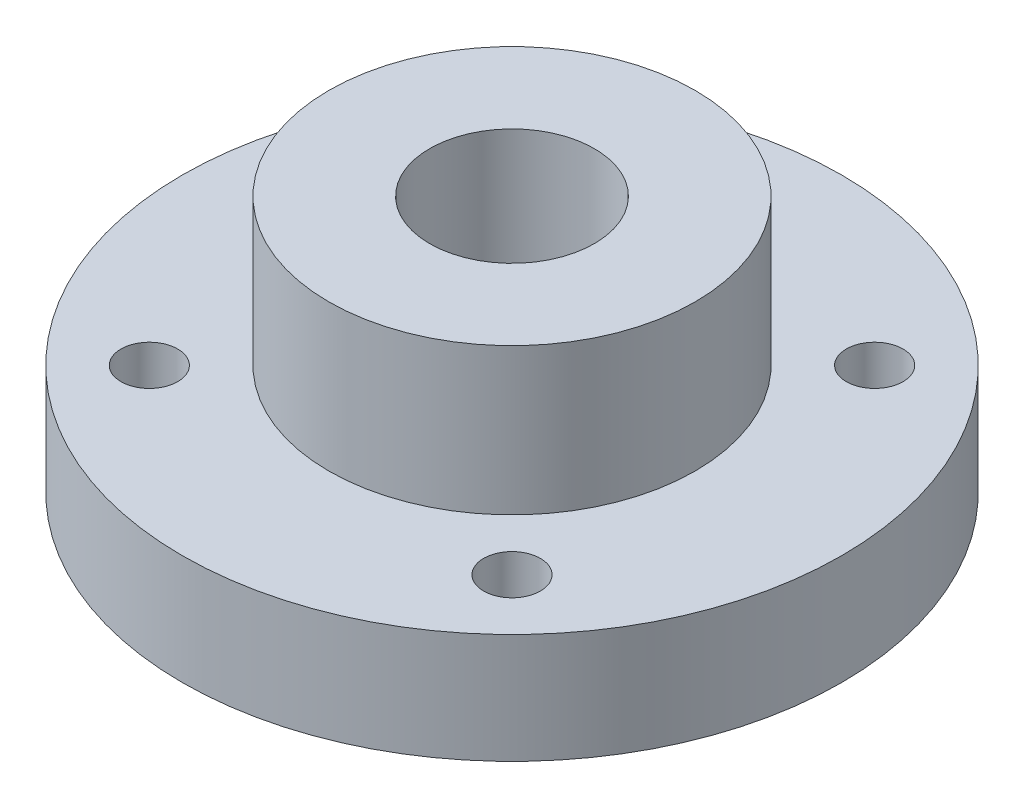
SolidWorks part; units mm, degrees
material "6061-T6 (SS)"
ref_plane "Front Plane" through (0, 0, 0) normal (0, 0, 1) x (1, 0, 0)
ref_plane "Top Plane" through (0, 0, 0) normal (0, 1, 0) x (1, 0, 0)
ref_plane "Right Plane" through (0, 0, 0) normal (1, 0, 0) x (0, 0, -1)
sketch "Sketch1" plane through (0, 0, 0) normal (0, 0, 1) x (1, 0, 0)
  line L0 (0, 0) -> (0, -14.566) construction
  line L6 (-11.1125, -70.6552) -> (-11.1125, -77.0052)
  line L7 (-15.875, -51.6052) -> (-15.875, -64.3052)
  line L8 (-15.875, -64.3052) -> (-28.575, -64.3052)
  line L9 (-28.575, -64.3052) -> (-28.575, -73.8302)
  line L12 (76.2, -73.8302) -> (-76.2, -73.8302) construction
  line L14 (-14.1605, -73.8302) -> (-14.1605, -77.0052)
  line L15 (-14.1605, -77.0052) -> (-11.1125, -77.0052)
  line L17 (-28.575, -73.8302) -> (-19.05, -73.8302)
  line L18 (-19.05, -73.8302) -> (-19.05, -70.6933)
  line L19 (-19.05, -70.6933) -> (-14.1605, -70.6933)
  line L20 (-14.1605, -70.6933) -> (-14.1605, -73.8302)
  line L21 (-15.875, -51.6052) -> (-4.7625, -51.6052)
  line L22 (-4.7625, -51.6052) -> (-4.7625, -70.6552)
  line L23 (-4.7625, -70.6552) -> (-11.1125, -70.6552)
  dimension "D2" = 22.225
  dimension "D3" = 9.525
  dimension "D4" = 9.525
  dimension "D5" = 6.35
  dimension "D6" = 12.7
  dimension "D7" = 57.15
  dimension "D8" = 19.05
  dimension "D9" = 28.321
  dimension "D11" = 3.175
  dimension "D12" = 38.1
  dimension "D13" = 3.1369
revolve "Revolve1" add sketch "Sketch1" angle 360 about L0
hole_wizard "#10 (0.1935) Diameter Hole1" positions "Sketch2" profile "Sketch3" hole size "#10" standard "ANSI Inch" end condition through all
sketch "Sketch2" plane through (0, -51.6052, 0) normal (0, 1, 0) x (1, 0, 0)
  line L0 (-15.7154, 15.7154) -> (15.7154, -15.7154) construction
  line L2 (15.7154, 15.7154) -> (-15.7154, -15.7154) construction
  line L3 (0, 0) -> (-24.6236, 0) construction
  point P0 (15.7154, 15.7154)
  point P2 (-15.7154, 15.7154)
  point P4 (-15.7154, -15.7154)
  point P6 (15.7154, -15.7154)
  dimension "D1" = 44.45
  dimension "D2" = 45
sketch "Sketch3" plane through (15.7154, -51.6052, -15.7154) normal (1, 0, 0) x (0, 0, 1)
  line L0 (0, 0) -> (0, 25.4)
  line L1 (0, 25.4) -> (2.4574, 25.4)
  line L2 (2.4574, 25.4) -> (2.4574, 0)
  line L5 (2.4574, 0) -> (0, 0)
  line L11 (0, -6.35) -> (0, 107.95) construction
  dimension "Thru Hole Dia." = 4.9149
  dimension "Thru Hole Depth" = 25.4
hole_wizard "Pipe Tap Drill for 3/8 Tap1" positions "3DSketch1" profile "Sketch4" hole size "3/8" standard "ANSI Inch"
sketch3d "3DSketch1"
  circle A1 centre (0, -51.6052, 0) radius 15.875 construction
  point P0 (0, -51.6052, 0)
  point P9 (0, -35.7302, 0)
sketch "Sketch4" plane through (0, -51.6052, 0) normal (1, 0, 0) x (0, 0, 1)
  line L0 (0, 0) -> (0, 18.5761)
  line L1 (0, 18.5761) -> (7.1374, 14.2875)
  line L2 (7.1374, 14.2875) -> (7.1374, 0)
  line L5 (7.1374, 0) -> (0, 0)
  line L10 (0, 18.5761) -> (-7.1374, 14.2875) construction
  line L11 (0, -6.35) -> (0, 107.95) construction
  dimension "Hole Dia." = 14.2748
  dimension "Hole Depth" = 14.2875
  dimension "Drill Angle" = 118
